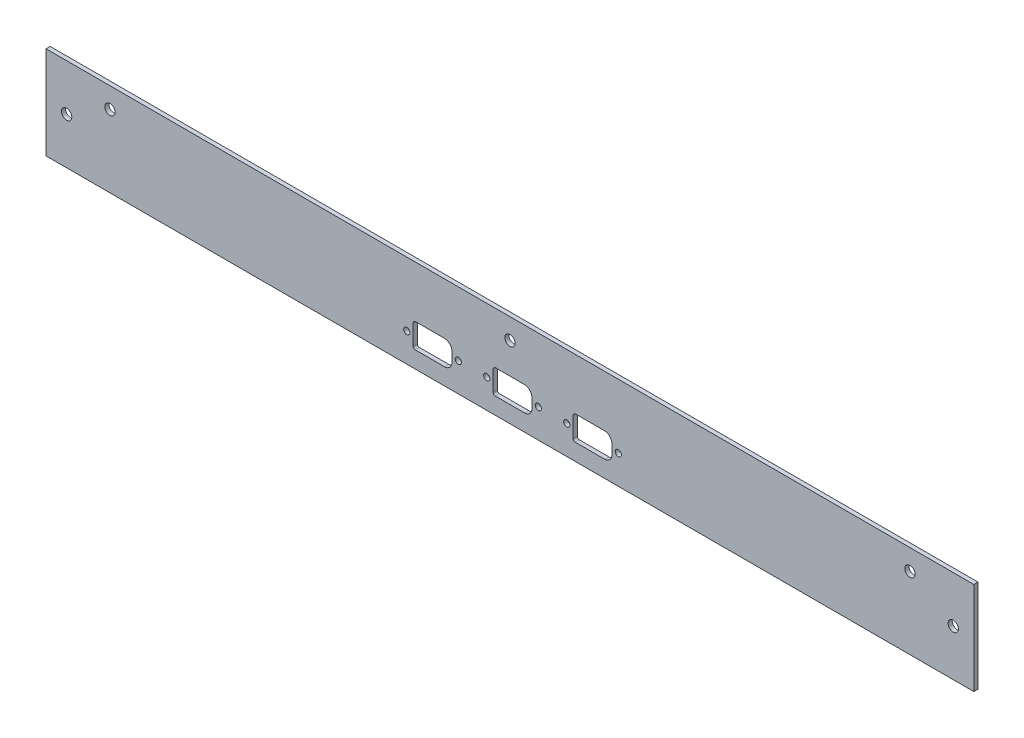
SolidWorks part; units mm, degrees
material "1345 Alloy"
ref_plane "Front Plane" through (0, 0, 0) normal (0, 0, 1) x (1, 0, 0)
ref_plane "Top Plane" through (0, 0, 0) normal (0, 1, 0) x (1, 0, 0)
ref_plane "Right Plane" through (0, 0, 0) normal (1, 0, 0) x (0, 0, -1)
sketch "Sketch1" plane through (0, 0, 0) normal (0, 0, 1) x (1, 0, 0)
  line L1 (-225, 22.5) -> (225, 22.5)
  line L2 (-225, 22.5) -> (-225, -22.5)
  line L3 (-225, -22.5) -> (225, -22.5)
  line L4 (225, 22.5) -> (225, -22.5)
  line L5 (-225, 22.5) -> (225, -22.5) construction
  line L6 (-225, -22.5) -> (225, 22.5) construction
  point P0 (0, 0)
  dimension "D1" = 450
  dimension "D2" = 45
extrude "Boss-Extrude1" add sketch "Sketch1" along normal blind 2
sketch "Sketch2" plane through (0, 0, 2) normal (0, 0, 1) x (1, 0, 0)
  line L0 (-28.1375, -8.55) -> (-25.0375, -8.55) construction
  line L1 (-31.6625, -14.4) -> (-45.9375, -14.4)
  line L2 (-45.7375, -2.5) -> (-31.8625, -2.5)
  line L3 (-46.9375, -13.4) -> (-46.9375, -3.7)
  line L4 (-28.1375, -10.875) -> (-28.1375, -6.225)
  line L5 (7.1375, -14.4) -> (-7.1375, -14.4)
  line L6 (-6.9375, -2.5) -> (6.9375, -2.5)
  line L7 (-8.1375, -13.4) -> (-8.1375, -3.7)
  line L8 (10.6625, -10.875) -> (10.6625, -6.225)
  line L9 (45.9375, -14.4) -> (31.6625, -14.4)
  line L10 (31.8625, -2.5) -> (45.7375, -2.5)
  line L11 (30.6625, -13.4) -> (30.6625, -3.7)
  line L12 (49.4625, -10.875) -> (49.4625, -6.225)
  line L17 (10.6625, -8.55) -> (13.7625, -8.55) construction
  line L18 (0, 22.5) -> (-225, 22.5) construction
  line L23 (-25.0375, -8.55) -> (-11.2375, -8.55) construction
  line L24 (-50.0375, -8.55) -> (-46.9375, -8.55) construction
  line L25 (-11.2375, -8.55) -> (-8.1375, -8.55) construction
  line L26 (27.5625, -8.55) -> (30.6625, -8.55) construction
  line L27 (-11.2375, -8.55) -> (-8.1375, -8.55) construction
  line L28 (13.7625, -8.55) -> (27.5625, -8.55) construction
  line L29 (49.4625, -8.55) -> (52.5625, -8.55) construction
  line L32 (0, -2.5) -> (0, 22.5) construction
  arc A0 (-28.1375, -10.875) -> (-31.6625, -14.4) centre (-31.6625, -10.875) cw
  arc A1 (-28.1375, -6.225) -> (-31.8625, -2.5) centre (-31.8625, -6.225) ccw
  arc A2 (-45.9375, -14.4) -> (-46.9375, -13.4) centre (-45.9375, -13.4) cw
  arc A3 (-46.9375, -3.7) -> (-45.7375, -2.5) centre (-45.7375, -3.7) cw
  arc A4 (10.6625, -10.875) -> (7.1375, -14.4) centre (7.1375, -10.875) cw
  arc A5 (10.6625, -6.225) -> (6.9375, -2.5) centre (6.9375, -6.225) ccw
  arc A6 (-7.1375, -14.4) -> (-8.1375, -13.4) centre (-7.1375, -13.4) cw
  arc A7 (-8.1375, -3.7) -> (-6.9375, -2.5) centre (-6.9375, -3.7) cw
  arc A8 (49.4625, -10.875) -> (45.9375, -14.4) centre (45.9375, -10.875) cw
  arc A9 (49.4625, -6.225) -> (45.7375, -2.5) centre (45.7375, -6.225) ccw
  arc A10 (31.6625, -14.4) -> (30.6625, -13.4) centre (31.6625, -13.4) cw
  arc A11 (30.6625, -3.7) -> (31.8625, -2.5) centre (31.8625, -3.7) cw
  circle A20 centre (-50.0375, -8.55) radius 1.5
  circle A21 centre (-25.0375, -8.55) radius 1.5
  circle A22 centre (-11.2375, -8.55) radius 1.5
  circle A23 centre (13.7625, -8.55) radius 1.5
  circle A24 centre (27.5625, -8.55) radius 1.5
  circle A25 centre (52.5625, -8.55) radius 1.5
  dimension "D5" = 3
  dimension "D6" = 3
  dimension "D1" = 3
  dimension "D2" = 3
  dimension "D3" = 3
  dimension "D4" = 3
  dimension "D7" = 25
  dimension "D9" = 13.8
  dimension "D10" = 13.8
  dimension "D11" = 25
  dimension "D12" = 25
  dimension "D13" = 5.85
  dimension "D14" = 5.85
  dimension "D15" = 5.85
  dimension "D16" = 5.85
  dimension "D17" = 5.85
  dimension "D18" = 5.85
extrude "Cut-Extrude1" cut sketch "Sketch2" against normal through all
sketch "Sketch3" plane through (0, 0, 2) normal (0, 0, 1) x (1, 0, 0)
  line L0 (-225, 22.5) -> (-215, 22.5) construction
  line L1 (225, 22.5) -> (-225, 22.5) construction
  line L2 (-215, 22.5) -> (-215, 0) construction
  line L3 (225, -22.5) -> (225, 22.5) construction
  line L4 (-194, 12.4954) -> (194, 12.4954) construction
  line L5 (-225, 22.5) -> (-225, -22.5) construction
  line L7 (0, 22.5) -> (0, 12.5) construction
  circle A0 centre (-215, 0) radius 2.5
  circle A1 centre (215, 0) radius 2.5
  circle A2 centre (-194, 12.4954) radius 2.5
  circle A3 centre (194, 12.4954) radius 2.5
  circle A4 centre (0, 12.5) radius 2.5
  dimension "D3" = 5
  dimension "D6" = 5
  dimension "D7" = 5
  dimension "D8" = 5
  dimension "D9" = 5
  dimension "D1" = 10
  dimension "D2" = 22.5
  dimension "D4" = 2
  dimension "D5" = 10
  dimension "D10" = 10
  dimension "D11" = 31
  dimension "D12" = 31
extrude "Cut-Extrude2" cut sketch "Sketch3" against normal through all
